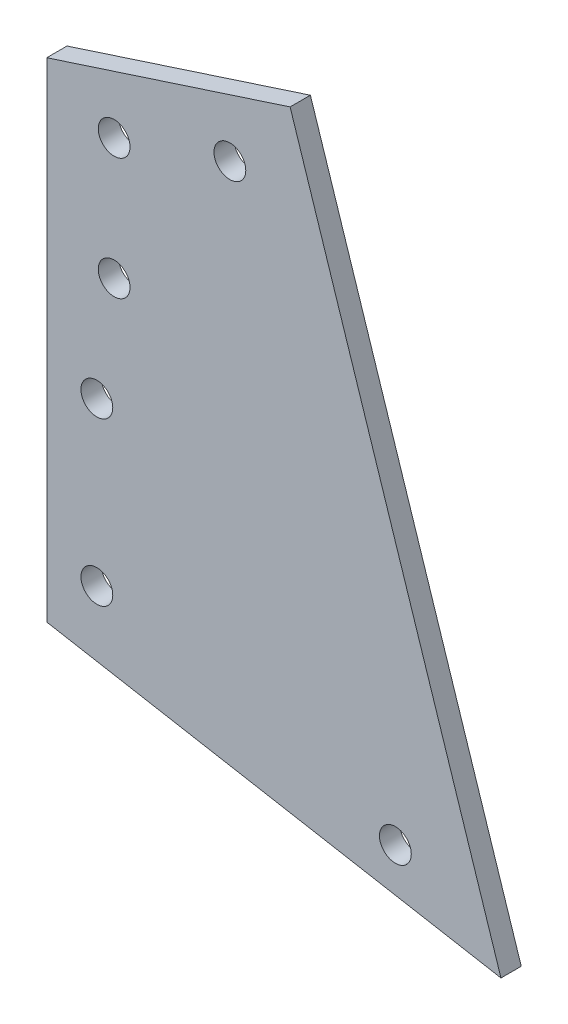
SolidWorks part; units mm, degrees
ref_plane "Front Plane" through (0, 0, 0) normal (0, 0, 1) x (1, 0, 0)
ref_plane "Top Plane" through (0, 0, 0) normal (0, 1, 0) x (1, 0, 0)
ref_plane "Right Plane" through (0, 0, 0) normal (1, 0, 0) x (0, 0, -1)
sketch "Sketch2" plane through (0, 0, 0) normal (0, 0, 1) x (1, 0, 0)
  line L0 (40.992, 298.8407) -> (42.9542, 292.8015) construction
  line L2 (40.992, 298.8407) -> (53.3542, 260.7936) construction
  line L6 (201.5046, -195.1666) -> (40.992, 298.8407) construction
  line L7 (75.9661, 191.2015) -> (42.9542, 292.8015)
  line L8 (4.8542, 280.422) -> (4.8542, 203.9015)
  line L9 (4.8542, 203.9015) -> (75.9661, 191.2015)
  line L10 (12.7, 238.125) -> (12.7, 212.725) construction
  line L11 (52.6739, 180.6913) -> (64.7523, 184.6158) construction
  line L12 (177.3478, -203.0157) -> (25.4, 264.6316) construction
  line L13 (64.7523, 184.6158) -> (29.6006, 292.8015) construction
  line L14 (42.9542, 292.8015) -> (4.8542, 280.422)
extrude "Boss-Extrude1" add sketch "Sketch2" along normal blind 3.175
sketch "Sketch3" plane through (0, 0, 3.175) normal (0, 0, 1) x (1, 0, 0)
  line L0 (75.9661, 191.2015) -> (63.8876, 187.2769) construction
  line L1 (63.8876, 187.2769) -> (29.6006, 292.8015) construction
  line L3 (61.7899, 193.7332) -> (59.4352, 200.9803) construction
  line L4 (4.8542, 203.9015) -> (75.9661, 191.2015) construction
  line L5 (29.6006, 292.8015) -> (33.5252, 280.723) construction
  line L6 (33.5252, 280.723) -> (15.4075, 274.8363) construction
  line L7 (15.4075, 274.8363) -> (15.4075, 255.7863) construction
hole_wizard "#10 Clearance Hole1" positions "Sketch4" profile "Sketch5" hole size "#10" standard "ANSI Inch" end condition through all
sketch "Sketch4" plane through (0, 0, 3.175) normal (0, 0, 1) x (1, 0, 0)
  point P0 (33.5252, 280.723)
  point P3 (59.4352, 200.9803)
  point P7 (12.7, 238.125)
  point P10 (12.7, 212.725)
  point P14 (15.4075, 274.8363)
  point P17 (15.4075, 255.7863)
sketch "Sketch5" plane through (33.5252, 280.723, 3.175) normal (1, 0, 0) x (0, -1, 0)
  line L0 (0, 0) -> (0, 3.175)
  line L1 (0, 3.175) -> (2.4892, 3.175)
  line L2 (2.4892, 3.175) -> (2.4892, 0)
  line L5 (2.4892, 0) -> (0, 0)
  line L11 (0, -6.35) -> (0, 107.95) construction
  dimension "Thru Hole Dia." = 4.9784
  dimension "Thru Hole Depth" = 3.175
